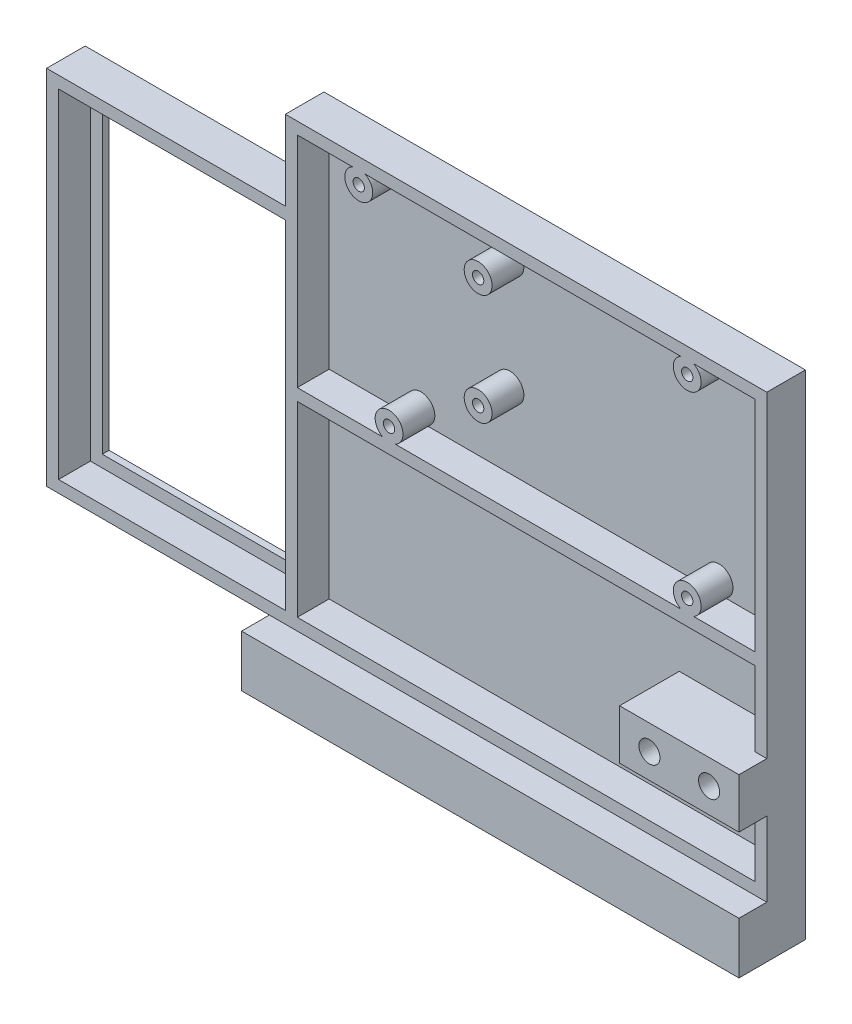
SolidWorks part; units mm, degrees
material "ABS"
ref_plane "Front Plane" through (0, 0, 0) normal (0, 0, 1) x (1, 0, 0)
ref_plane "Top Plane" through (0, 0, 0) normal (0, 1, 0) x (1, 0, 0)
ref_plane "Right Plane" through (0, 0, 0) normal (1, 0, 0) x (0, 0, -1)
sketch "Sketch1" plane through (0, 0, 0) normal (0, 0, 1) x (1, 0, 0)
  line L0 (-45.5, -31.5) -> (-45.5, 31.5) construction
  line L1 (-42.5, -28.5) -> (42.5, -28.5)
  line L2 (-42.5, -28.5) -> (-42.5, 28.5)
  line L3 (-42.5, 28.5) -> (42.5, 28.5)
  line L4 (42.5, -28.5) -> (42.5, 28.5)
  line L5 (-42.5, -28.5) -> (42.5, 28.5) construction
  line L6 (-42.5, 28.5) -> (42.5, -28.5) construction
  line L7 (-45.5, -81.5) -> (75.5, -81.5) construction
  line L8 (-45.5, -81.5) -> (-45.5, -31.5) construction
  line L9 (-45.5, -31.5) -> (75.5, -31.5) construction
  line L10 (75.5, -81.5) -> (75.5, -31.5) construction
  line L11 (-45.5, -81.5) -> (75.5, -31.5) construction
  line L12 (-45.5, -31.5) -> (75.5, -81.5) construction
  line L17 (-45.5, 31.5) -> (45.5, 31.5) construction
  line L18 (45.5, -31.5) -> (45.5, 31.5) construction
  line L19 (-45.5, -31.5) -> (45.5, -31.5) construction
  line L21 (45.5, 31.5) -> (75.5, 31.5) construction
  line L22 (45.5, 31.5) -> (45.5, -31.5) construction
  line L23 (45.5, -31.5) -> (75.5, -31.5) construction
  line L24 (75.5, 31.5) -> (75.5, -31.5) construction
  line L25 (-45.5, 31.5) -> (75.5, 31.5)
  line L26 (-45.5, 31.5) -> (-45.5, -81.5)
  line L27 (-45.5, -81.5) -> (75.5, -81.5)
  line L28 (75.5, 31.5) -> (75.5, -81.5)
  circle A0 centre (68, -56.5) radius 2.65
  circle A1 centre (53, -56.5) radius 2.65
  circle A2 centre (51, -21.5) radius 1.425
  circle A3 centre (68, -21.5) radius 1.425
  point P0 (0, 0)
  point P6 (15, -56.5)
  dimension "D4" = 15
  dimension "D5" = 7.5
  dimension "D6" = 5.3
  dimension "D10" = 2.85
  dimension "D1" = 85
  dimension "D2" = 57
  dimension "D3" = 50
  dimension "D7" = 30
  dimension "D8" = 10
  dimension "D11" = 17
  dimension "D9" = 3
extrude "Boss-Extrude1" add sketch "Sketch1" along normal blind 10
sketch "Sketch2" plane through (0, 0, 0) normal (0, 0, -1) x (-1, 0, 0)
  line L1 (-42.5, 28.5) -> (42.5, 28.5)
  line L2 (-42.5, 28.5) -> (-42.5, -28.5)
  line L3 (-42.5, -28.5) -> (42.5, -28.5)
  line L4 (42.5, 28.5) -> (42.5, -28.5)
extrude "Boss-Extrude2" add sketch "Sketch2" against normal blind 2
sketch "Sketch4" plane through (0, 0, 10) normal (0, 0, 1) x (1, 0, 0)
  line L0 (-42.5, 28.5) -> (-45.5, 31.5) construction
  line L1 (-45.5, 31.5) -> (45.5, 31.5)
  line L2 (-45.5, 31.5) -> (-45.5, -31.5)
  line L3 (-45.5, -31.5) -> (45.5, -31.5)
  line L4 (45.5, 31.5) -> (45.5, -31.5)
  line L5 (42.5, -28.5) -> (45.5, -31.5) construction
  line L6 (-45.5, -31.5) -> (-45.5, -81.5)
  line L7 (-45.5, -81.5) -> (75.5, -81.5)
  line L8 (75.5, -81.5) -> (75.5, 31.5)
  line L9 (75.5, 31.5) -> (45.5, 31.5)
  line L10 (45.5, -31.5) -> (45.5, 31.5)
  line L11 (-45.5, -31.5) -> (45.5, -31.5)
  line L12 (-45.5, -81.5) -> (-45.5, -31.5)
  line L13 (53, -56.5) -> (68, -56.5) construction
  line L14 (-42.5, -28.5) -> (-42.5, -78.5)
  line L15 (45.5, -62.75) -> (75.5, -62.75)
  line L16 (45.5, -62.75) -> (45.5, -50.25)
  line L17 (45.5, -50.25) -> (75.5, -50.25)
  line L18 (75.5, -62.75) -> (75.5, -50.25)
  line L19 (45.5, -62.75) -> (75.5, -50.25) construction
  line L20 (45.5, -50.25) -> (75.5, -62.75) construction
  line L21 (-42.5, -78.5) -> (72.5, -78.5)
  line L22 (72.5, -78.5) -> (72.5, -62.75)
  line L23 (45.5, 28.5) -> (72.5, 28.5)
  line L24 (72.5, 28.5) -> (72.5, -21.5)
  line L25 (72.5, -21.5) -> (72.5, -50.25)
  line L26 (-42.5, -78.5) -> (-45.5, -81.5) construction
  line L27 (72.5, -78.5) -> (75.5, -81.5) construction
  line L28 (72.5, 28.5) -> (75.5, 31.5) construction
  line L29 (51, -21.5) -> (68, -21.5) construction
  line L31 (73.5, -26) -> (45.5, -26)
  line L32 (73.5, -26) -> (73.5, -17)
  line L33 (73.5, -17) -> (45.5, -17)
  line L34 (45.5, -26) -> (45.5, -17)
  line L35 (73.5, -26) -> (45.5, -17) construction
  line L36 (73.5, -17) -> (45.5, -26) construction
  circle A2 centre (53, -56.5) radius 2.65
  circle A3 centre (68, -56.5) radius 2.65
  circle A6 centre (68, -56.5) radius 2.65 construction
  point P21 (60.5, -56.5)
  point P29 (59.5, -21.5)
  dimension "D2" = 9
  dimension "D1" = 12.5
extrude "Cut-Extrude1" cut sketch "Sketch4" against normal up to surface (8 mm away) contours L33 L24 L23 L10 | L25 L31 L4 L11 L14 L21 L22 L15 L16 L17 region at (59, 5.75, 10) region at (13.4057, -54.1556, 10) up to face at (0, 0, 2)
sketch "Sketch5" plane through (0, 0, 0) normal (0, 0, -1) x (-1, 0, 0)
  line L1 (-64.25, -25.25) -> (-71.75, -25.25) construction
  line L2 (-64.25, -25.25) -> (-64.25, -17.75) construction
  line L3 (-64.25, -17.75) -> (-71.75, -17.75) construction
  line L4 (-71.75, -25.25) -> (-71.75, -17.75) construction
  line L5 (-64.25, -25.25) -> (-71.75, -17.75) construction
  line L6 (-64.25, -17.75) -> (-71.75, -25.25) construction
  line L7 (-47.25, -25.25) -> (-54.75, -25.25) construction
  line L8 (-47.25, -25.25) -> (-47.25, -17.75) construction
  line L9 (-47.25, -17.75) -> (-54.75, -17.75) construction
  line L10 (-54.75, -25.25) -> (-54.75, -17.75) construction
  line L11 (-47.25, -25.25) -> (-54.75, -17.75) construction
  line L12 (-47.25, -17.75) -> (-54.75, -25.25) construction
  line L13 (-73.25, -61.75) -> (-62.75, -61.75)
  line L14 (-73.25, -61.75) -> (-73.25, -51.25)
  line L15 (-73.25, -51.25) -> (-62.75, -51.25)
  line L16 (-62.75, -61.75) -> (-62.75, -51.25)
  line L17 (-73.25, -61.75) -> (-62.75, -51.25) construction
  line L18 (-73.25, -51.25) -> (-62.75, -61.75) construction
  line L19 (-47.75, -61.75) -> (-58.25, -61.75)
  line L20 (-47.75, -61.75) -> (-47.75, -51.25)
  line L21 (-47.75, -51.25) -> (-58.25, -51.25)
  line L22 (-58.25, -61.75) -> (-58.25, -51.25)
  line L23 (-47.75, -61.75) -> (-58.25, -51.25) construction
  line L24 (-47.75, -51.25) -> (-58.25, -61.75) construction
  point P0 (-68, -21.5)
  point P6 (-51, -21.5)
  point P12 (-68, -56.5)
  point P18 (-53, -56.5)
  dimension "D1" = 7.5
  dimension "D2" = 10.5
extrude "Cut-Extrude2" cut sketch "Sketch5" against normal blind 7
sketch "Sketch7" plane through (0, 0, 10) normal (0, 0, 1) x (1, 0, 0)
  line L0 (75.5, -81.5) -> (75.5, 31.5) construction
  line L1 (45.5, -50.25) -> (75.5, -50.25)
  line L2 (45.5, -50.25) -> (45.5, -62.75)
  line L3 (45.5, -62.75) -> (75.5, -62.75)
  line L4 (75.5, -50.25) -> (75.5, -62.75)
  line L5 (45.5, -62.75) -> (72.5, -62.75) construction
  circle A0 centre (51, -21.5) radius 1.425
  circle A1 centre (51, -21.5) radius 3
  circle A2 centre (68, -21.5) radius 3
  circle A3 centre (68, -21.5) radius 1.425
  circle A4 centre (53, -56.5) radius 2.65
  circle A5 centre (68, -56.5) radius 2.65
  circle A6 centre (53, -56.5) radius 2.65 construction
  circle A7 centre (51, -21.5) radius 1.425 construction
  dimension "D1" = 6
extrude "Boss-Extrude4" add sketch "Sketch7" along normal blind 7
chamfer "Chamfer2" distance 2 distance2 7 2 edges at (65, -21.5, 10) (48, -21.5, 10) first distance on face at (65, -21.5, 10)
sketch "Sketch9" plane through (0, 0, 0) normal (0, 0, -1) x (-1, 0, 0)
  line L0 (45.5, -81.5) -> (-75.5, -81.5) construction
  line L1 (45.5, 31.5) -> (100.5, 31.5)
  line L2 (45.5, 31.5) -> (45.5, -81.5)
  line L3 (45.5, -81.5) -> (100.5, -81.5)
  line L4 (100.5, 31.5) -> (100.5, -81.5)
  dimension "D1" = 55
extrude "Boss-Extrude5" add sketch "Sketch9" against normal up to surface (17 mm away) up to face at (54, -21.5, 17)
sketch "Sketch10" plane through (0, 0, 17) normal (0, 0, 1) x (1, 0, 0)
  line L1 (-90.5, -73.5) -> (-50.5, -73.5) construction
  line L2 (-90.5, -73.5) -> (-90.5, -13.5) construction
  line L3 (-90.5, -13.5) -> (-50.5, -13.5) construction
  line L4 (-50.5, -73.5) -> (-50.5, -13.5) construction
  line L5 (-90.5, -73.5) -> (-50.5, -13.5) construction
  line L6 (-90.5, -13.5) -> (-50.5, -73.5) construction
  line L7 (-45.5, 31.5) -> (-45.5, -81.5) construction
  line L8 (-45.5, -78.5) -> (-95.5, -78.5) construction
  line L9 (-45.5, -78.5) -> (-45.5, -8.5) construction
  line L10 (-45.5, -8.5) -> (-95.5, -8.5) construction
  line L11 (-95.5, -78.5) -> (-95.5, -8.5) construction
  line L12 (-45.5, -78.5) -> (-95.5, -8.5) construction
  line L13 (-45.5, -8.5) -> (-95.5, -78.5) construction
  line L14 (-45.5, 31.5) -> (-45.5, -81.5) construction
  circle A0 centre (-90.5, -13.5) radius 1.425
  circle A1 centre (-50.5, -13.5) radius 1.425
  circle A2 centre (-90.5, -73.5) radius 1.425
  circle A3 centre (-50.5, -73.5) radius 1.425
  point P0 (-70.5, -43.5)
  point P9 (-70.5, -43.5)
  dimension "D3" = 2.85
  dimension "D1" = 60
  dimension "D2" = 40
  dimension "D4" = 50
  dimension "D5" = 70
extrude "Cut-Extrude3" cut sketch "Sketch10" against normal through all
sketch "Sketch11" plane through (0, 0, 17) normal (0, 0, 1) x (1, 0, 0)
  line L0 (-48.5, 28.5) -> (-45.5, 28.5)
  line L1 (-45.5, 31.5) -> (-45.5, -81.5) construction
  line L2 (-48.5, -78.5) -> (-45.5, -78.5)
  line L3 (-45.5, 31.5) -> (-45.5, -81.5) construction
  line L4 (-45.5, -78.5) -> (-45.5, 28.5)
  line L8 (-48.5, -78.5) -> (-48.5, 28.5)
  line L9 (-48.5, 28.5) -> (-97.5, 28.5)
  line L10 (-97.5, 28.5) -> (-97.5, -78.5)
  line L11 (-97.5, -78.5) -> (-48.5, -78.5)
  line L12 (-48.5, -78.5) -> (-48.5, 28.5) construction
  line L13 (-48.5, 28.5) -> (-97.5, 28.5)
  line L14 (-97.5, 28.5) -> (-97.5, -78.5)
  line L15 (-97.5, -78.5) -> (-48.5, -78.5)
  circle A0 centre (-90.5, -13.5) radius 3.5
  circle A1 centre (-50.5, -13.5) radius 3.5
  circle A2 centre (-90.5, -73.5) radius 3.5
  circle A3 centre (-50.5, -73.5) radius 3.5
  line M10 (-45.5, -81.5) -> (-45.5, 31.5)
  dimension "D1" = 7
  dimension "D2" = 3
extrude "Cut-Extrude4" cut sketch "Sketch11" against normal up to surface (15 mm away) contours L15 L12 L13 A1 A0 L14 A2 A3 | L12 L2 L0 M10 region at (-46.9653, -24.2757, 17) region at (-73.0159, -24.4856, 17) up to face at (0, 0, 2)
sketch "Sketch12" plane through (0, 0, 17) normal (0, 0, 1) x (1, 0, 0)
  line L5 (-100.5, -81.5) -> (-45.5, -81.5)
  line L6 (-100.5, -81.5) -> (-100.5, 31.5)
  line L7 (-100.5, 31.5) -> (-45.5, 31.5)
  line L8 (-45.5, -81.5) -> (-45.5, 31.5)
  circle A0 centre (-90.5, -13.5) radius 3.5
  circle A1 centre (-50.5, -13.5) radius 3.5
  circle A2 centre (-90.5, -73.5) radius 3.5
  circle A3 centre (-50.5, -73.5) radius 3.5
  circle A4 centre (-90.5, -73.5) radius 3.5 construction
extrude "Cut-Extrude5" cut sketch "Sketch12" against normal up to surface (7 mm away) up to face at (37.0833, -29.625, 10)
sketch "Sketch13" plane through (0, -81.5, 0) normal (0, -1, 0) x (1, 0, 0)
  line L0 (71.5, 4) -> (-45.5, 4) construction
  line L1 (-49.5, 0) -> (75.5, 0)
  line L2 (-49.5, 0) -> (-49.5, 17)
  line L3 (-49.5, 17) -> (75.5, 17)
  line L4 (75.5, 0) -> (75.5, 17)
  line L5 (42.25, 4) -> (-16.25, 4) construction
  line L6 (-100.5, 0) -> (75.5, 0) construction
  line L7 (13, 4) -> (-16.25, 4) construction
  line L8 (-16.25, 4) -> (-45.5, 4) construction
  circle A0 centre (71.5, 4) radius 4 construction
  circle A1 centre (-45.5, 4) radius 4 construction
  circle A2 centre (-16.25, 4) radius 1.9
  circle A3 centre (42.25, 4) radius 1.9
  circle A4 centre (71.5, 4) radius 1.9
  circle A5 centre (-45.5, 4) radius 1.9
  point P9 (13, 4)
  point P12 (13, 4)
  dimension "D1" = 8
  dimension "D3" = 3.8
  dimension "D2" = 125
extrude "Boss-Extrude6" add sketch "Sketch13" along normal blind 13
sketch "Sketch16" plane through (0, 0, 17) normal (0, 0, 1) x (1, 0, 0)
  line L1 (-45.5, -78.5) -> (-102.5, -78.5)
  line L2 (-45.5, -78.5) -> (-45.5, 6.5)
  line L3 (-45.5, 6.5) -> (-102.5, 6.5)
  line L4 (-102.5, -78.5) -> (-102.5, 6.5)
  dimension "D1" = 85
  dimension "D2" = 57
extrude "Cut-Extrude7" cut sketch "Sketch16" against normal up to surface (15 mm away) up to face at (-94, -73.5, 2)
sketch "Sketch17" plane through (0, 0, 10) normal (0, 0, 1) x (1, 0, 0)
  line L0 (-42.5, -81.5) -> (-42.5, 9.5)
  line L1 (-45.5, -78.5) -> (-102.5, -78.5)
  line L2 (-45.5, -78.5) -> (-45.5, 6.5)
  line L3 (-45.5, 6.5) -> (-102.5, 6.5)
  line L4 (-102.5, -78.5) -> (-102.5, 6.5)
  line L5 (-42.5, 9.5) -> (-105.5, 9.5)
  line L6 (-105.5, -81.5) -> (-105.5, 9.5)
  line L7 (-42.5, -81.5) -> (-105.5, -81.5)
  dimension "D1" = 57
  dimension "D2" = 85
  dimension "D3" = 3
extrude "Boss-Extrude8" add sketch "Sketch17" against normal up to surface (10 mm away) up to face at (-49.075, -13.5, 0)
sketch "Sketch18" plane through (0, 0, 10) normal (0, 0, 1) x (1, 0, 0)
  line L1 (-105.5, 9.5) -> (75.5, 9.5)
  line L2 (-105.5, 9.5) -> (-105.5, 31.5)
  line L3 (-105.5, 31.5) -> (75.5, 31.5)
  line L4 (75.5, 9.5) -> (75.5, 31.5)
extrude "Cut-Extrude8" cut sketch "Sketch18" against normal through all both and the other way through all
sketch "Sketch19" plane through (0, 0, 17) normal (0, 0, 1) x (1, 0, 0)
  line L1 (-42.5, -28.5) -> (75.5, -28.5)
  line L2 (-42.5, -28.5) -> (-42.5, 9.5)
  line L3 (-42.5, 9.5) -> (75.5, 9.5)
  line L4 (75.5, -28.5) -> (75.5, 9.5)
extrude "Cut-Extrude9" cut sketch "Sketch19" against normal up to surface (15 mm away) up to face at (0, -9.5, 2)
sketch "Sketch20" plane through (0, 0, 10) normal (0, 0, 1) x (1, 0, 0)
  line L0 (72.5, -28.5) -> (72.5, -50.25) construction
  line L1 (45.5, -28.5) -> (72.5, -28.5)
  line L2 (45.5, -28.5) -> (45.5, -31.5)
  line L3 (45.5, -31.5) -> (72.5, -31.5)
  line L4 (72.5, -28.5) -> (72.5, -31.5)
  line L5 (-42.5, -31.5) -> (45.5, -31.5) construction
  point P7 (45.5, -31.5)
extrude "Boss-Extrude9" add sketch "Sketch20" against normal up to surface (8 mm away) up to face at (32.3571, -38.6429, 2)
sketch "Sketch21" plane through (0, 0, 2) normal (0, 0, 1) x (1, 0, 0)
  line L5 (-42.5, -28.5) -> (62.5, -28.5) construction
  line L6 (-42.5, -28.5) -> (-42.5, 26.5) construction
  line L7 (-42.5, 26.5) -> (62.5, 26.5) construction
  line L8 (62.5, -28.5) -> (62.5, 26.5) construction
  line L9 (-42.5, -28.5) -> (72.5, -28.5) construction
  line L10 (-42.5, -28.5) -> (-42.5, 26.5) construction
  line L11 (-42.5, 26.5) -> (72.5, 26.5) construction
  line L12 (72.5, -28.5) -> (72.5, 26.5) construction
  line L13 (-45.5, -31.5) -> (-45.5, 29.5)
  line L14 (-45.5, 29.5) -> (75.5, 29.5)
  line L15 (75.5, -31.5) -> (75.5, 29.5)
  line L16 (-45.5, -31.5) -> (75.5, -31.5)
  line L17 (75.5, -28.5) -> (75.5, 9.5) construction
  line L19 (-105.5, 9.5) -> (-45.5, 9.5)
  line L20 (-105.5, 9.5) -> (-105.5, 29.5)
  line L21 (-105.5, 29.5) -> (-45.5, 29.5)
  line L22 (-45.5, 9.5) -> (-45.5, 29.5)
  line L23 (-105.5, -81.5) -> (-49.5, -81.5)
  line L24 (-105.5, -81.5) -> (-105.5, -94.5)
  line L25 (-105.5, -94.5) -> (-49.5, -94.5)
  line L26 (-49.5, -81.5) -> (-49.5, -94.5)
  line L27 (-102.5, 6.5) -> (-45.5, 6.5)
  line L28 (-102.5, 6.5) -> (-102.5, -78.5)
  line L29 (-102.5, -78.5) -> (-45.5, -78.5)
  line L30 (-45.5, 6.5) -> (-45.5, -78.5)
  line M5 (-42.5, -28.5) -> (75.5, -28.5)
  line M6 (75.5, -28.5) -> (75.5, 9.5)
  line M7 (75.5, 9.5) -> (-42.5, 9.5)
  line M8 (-42.5, 9.5) -> (-42.5, -28.5)
  circle M9 centre (68, -21.5) radius 1.425
  circle M10 centre (51, -21.5) radius 1.425
  dimension "D1" = 55
  dimension "D2" = 105
  dimension "D3" = 3
extrude "Boss-Extrude10" add sketch "Sketch21" against normal up to surface (2 mm away) contours M8 M5 M6 M7 M9 M10 | L13 L16 L15 L14 M5 M8 M7 | M9 | M10 | L21 L20 L19 L13 | L26 L23 L24 L25 | L30 L13 L27 L28 L29 region at (-74, -36, 2) region at (12.6783, 12.1564, 2) region at (-75.5, 19.5, 2) region at (16.3773, -9.4658, 2) region at (-77.5, -88, 2) region at (68, -21.5, 2) region at (51, -21.5, 2) up to face at (-26.5, -55.5, 0)
sketch "Sketch23" plane through (0, 0, 2) normal (0, 0, 1) x (1, 0, 0)
  line L5 (-45.5, -31.5) -> (-45.5, 29.5)
  line L6 (-42.5, -28.5) -> (72.5, -28.5)
  line L7 (-42.5, -28.5) -> (-42.5, 26.5)
  line L8 (-42.5, 26.5) -> (72.5, 26.5)
  line L9 (72.5, -28.5) -> (72.5, 26.5)
  line L10 (-45.5, 29.5) -> (75.5, 29.5)
  line L11 (75.5, -31.5) -> (75.5, 29.5)
  line L12 (-45.5, -31.5) -> (75.5, -31.5)
  line L13 (-42.5, -28.5) -> (75.5, -28.5) construction
  line L14 (75.5, -50.25) -> (75.5, -28.5) construction
  line L15 (75.5, -28.5) -> (75.5, 29.5) construction
  line L16 (55.5, 23.38) -> (55.5, -25.38) construction
  line L17 (55.5, -1) -> (75.5, -1) construction
  circle A0 centre (55.5, -25.38) radius 1.425
  circle A1 centre (55.5, 23.38) radius 1.425
  circle A2 centre (2.95, -9.68) radius 1.425
  circle A3 centre (-27.05, 23.38) radius 1.425
  circle A4 centre (-19.43, -25.38) radius 1.425
  circle A5 centre (2.95, 18.17) radius 1.425
  circle A6 centre (-27.05, 23.38) radius 3.5
  circle A7 centre (2.95, 18.17) radius 3.5
  circle A8 centre (2.95, -9.68) radius 3.5
  circle A9 centre (-19.43, -25.38) radius 3.5
  circle A10 centre (55.5, -25.38) radius 3.5
  circle A11 centre (55.5, 23.38) radius 3.5
  line M21 (-42.5, -28.5) -> (75.5, -28.5)
  line M22 (75.5, -28.5) -> (75.5, 29.5)
  line M23 (75.5, 29.5) -> (-105.5, 29.5)
  line M25 (-105.5, 9.5) -> (-42.5, 9.5)
  dimension "D9" = 2.85
  dimension "D11" = 7
  dimension "D1" = 3
  dimension "D2" = 74.93
  dimension "D3" = 55
  dimension "D4" = 48.76
  dimension "D5" = 82.55
  dimension "D6" = 5.21
  dimension "D7" = 27.85
  dimension "D8" = 30
  dimension "D10" = 20
extrude "Boss-Extrude11" add sketch "Sketch23" along normal up to surface (8 mm away) contours A11 L8 L9 L5 L7 A6 M21 M22 M23 M25 | L8 A6 A3 | A7 A5 | L8 A11 A1 | A8 A2 | L6 A9 A4 | L6 A10 A0 | L8 A11 | L8 A6 region at (-44.1582, 19.5, 2) region at (-21.2098, -22.4787, 2) region at (-27.05, 26.6527, 2) region at (-27.05, 26.4037, 2) region at (55.5, -28.4037, 2) region at (58.4013, 25.1598, 2) region at (55.5, 26.6527, 2) region at (-0.451, 18.17, 2) region at (-0.451, -9.68, 2) up to face at (10.7667, -48.5667, 10)
sketch "Sketch24" plane through (0, 0, 10) normal (0, 0, 1) x (1, 0, 0)
  line L1 (-105.5, 29.5) -> (-45.5, 29.5)
  line L2 (-105.5, 29.5) -> (-105.5, 9.5)
  line L3 (-105.5, 9.5) -> (-45.5, 9.5)
  line L4 (-45.5, 29.5) -> (-45.5, 9.5)
  line L5 (-105.5, -81.5) -> (-49.5, -81.5)
  line L6 (-105.5, -81.5) -> (-105.5, -94.5)
  line L7 (-105.5, -94.5) -> (-49.5, -94.5)
  line L8 (-49.5, -81.5) -> (-49.5, -94.5)
  line L16 (-48.5, -75.5) -> (-48.5, 3.5)
  line L17 (-48.5, 3.5) -> (-99.5, 3.5)
  line L18 (-99.5, 3.5) -> (-99.5, -75.5)
  line L19 (-99.5, -75.5) -> (-48.5, -75.5)
  line L20 (-48.5, -75.5) -> (-48.5, 3.5)
  line L21 (-48.5, 3.5) -> (-99.5, 3.5)
  line L22 (-99.5, 3.5) -> (-99.5, -75.5)
  line L23 (-99.5, -75.5) -> (-48.5, -75.5)
  dimension "D1" = 3
extrude "Cut-Extrude10" cut sketch "Sketch24" against normal through all both and the other way through all
chamfer "Chamfer3" distance 0.3 angle 45 20 edges at (68, -51.25, 0) (73.25, -56.5, 0) (68, -61.75, 0) (62.75, -56.5, 0) (53, -61.75, 0) (47.75, -56.5, 0) (53, -51.25, 0) (58.25, -56.5, 0) (-99.5, -36, 0) (-74, 3.5, 0) (-48.5, -36, 0) (-74, -75.5, 0) (-75.5, 9.5, 0) (-105.5, -36, 0) (-77.5, -81.5, 0) (-49.5, -88, 0) (13, -94.5, 0) (75.5, -32.5, 0) (15, 29.5, 0) (-45.5, 19.5, 0)
